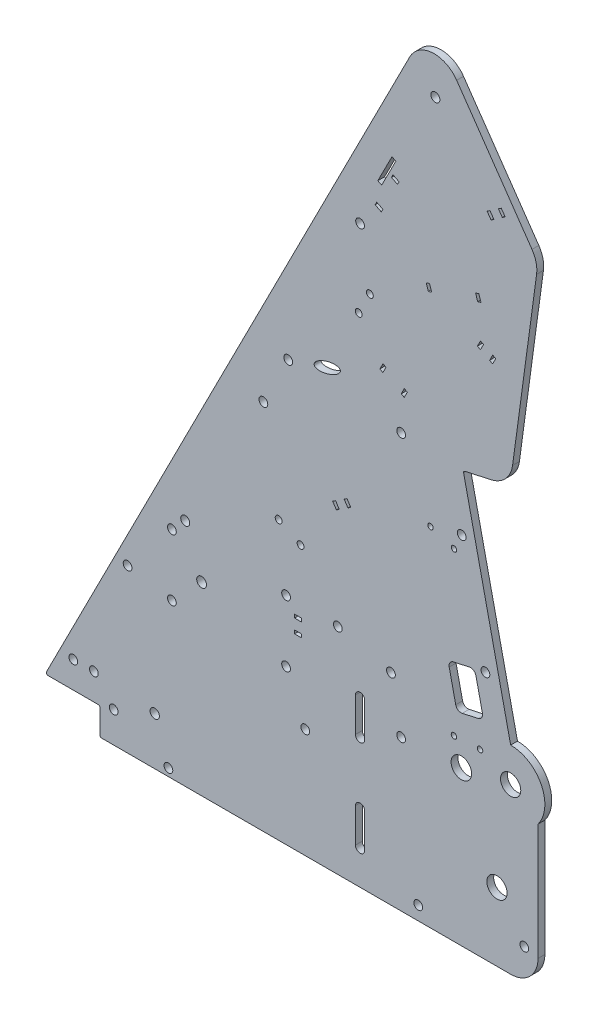
SolidWorks part; units mm, degrees
other "Markup1"
sketch "Sketch5"
ref_plane "Front Plane" through (0, 0, 0) normal (0, 0, 1) x (1, 0, 0)
ref_plane "Top Plane" through (0, 0, 0) normal (0, 1, 0) x (1, 0, 0)
ref_plane "Right Plane" through (0, 0, 0) normal (1, 0, 0) x (0, 0, -1)
sketch "Sketch1" plane through (0, 0, 0) normal (0, 0, 1) x (1, 0, 0)
  line L1 (228.6, -12.7) -> (228.6, 53.975)
  line L2 (178.7547, 351.4131) -> (0, 0)
  line L3 (228.6, 279.4) -> (178.7547, 351.4131)
  line L5 (0, 0) -> (25.4, 0)
  line L6 (25.4, 0) -> (25.4, -12.7)
  line L7 (25.4, -12.7) -> (228.6, -12.7)
  line L9 (215.9, 79.375) -> (193.9097, 178.5667)
  line L10 (193.9097, 178.5667) -> (215.6079, 183.377)
  line L11 (215.6079, 183.377) -> (228.6, 279.4)
  arc A0 (228.6, 53.975) -> (215.9, 79.375) centre (215.9, 63.5) ccw
  dimension "D7" = 12.7
  dimension "D8" = 76.2
  dimension "D10" = 31.75
  dimension "D2" = 292.1
  dimension "D3" = 25.4
  dimension "D4" = 215.9
  dimension "D5" = 394.2644
  dimension "D6" = 203.2
  dimension "D9" = 63.039
  dimension "D11" = 101.6
  dimension "D12" = 12.5
  dimension "D13" = 22.225
extrude "Boss-Extrude1" add sketch "Sketch1" along normal blind 3.175
sketch "Sketch2" plane through (0, 0, 3.175) normal (0, 0, 1) x (1, 0, 0)
  line L0 (178.7547, 351.4131) -> (0, 0) construction
  line L1 (25.4, -12.7) -> (228.6, -12.7) construction
  line L2 (215.9, 79.375) -> (193.9097, 178.5667) construction
  line L3 (193.9097, 178.5667) -> (215.6079, 183.377) construction
  line L4 (215.9, 79.375) -> (193.9097, 178.5667) construction
  line L5 (64.9432, 94.0578) -> (72.5445, 73.1732) construction
  line L6 (64.9432, 94.0578) -> (103.3734, 94.0578) construction
  line L10 (228.6, -12.7) -> (228.6, 53.975) construction
  circle A0 centre (64.9432, 94.0578) radius 2.0955
  circle A1 centre (180.975, 322.1643) radius 2.0955
  circle A2 centre (72.5445, 73.1732) radius 2.286
  circle A3 centre (193.2078, 152.3944) radius 2.032
  circle A4 centre (215.9, 63.5) radius 4.699
  circle A7 centre (173.0375, -6.35) radius 2.032
  circle A8 centre (204.203, 102.7985) radius 2.032
  circle A26 centre (209.55, 19.05) radius 4.699
  arc A30 (228.6, 53.975) -> (215.9, 79.375) centre (215.9, 63.5) ccw construction
  circle A31 centre (165.1, 179.3875) radius 2.032
  circle A35 centre (111.724, 87.4607) radius 2.032
  circle A36 centre (111.724, 58.8857) radius 2.032
  circle A37 centre (58.765, 58.8857) radius 2.032
  circle A38 centre (58.765, 87.4607) radius 2.032
  circle A39 centre (111.724, 58.8857) radius 1.905 construction
  circle A42 centre (111.724, 87.4607) radius 1.905 construction
  circle A43 centre (58.765, 58.8857) radius 1.905 construction
  circle A44 centre (58.765, 87.4607) radius 1.905 construction
  dimension "D3" = 4.191
  dimension "D5" = 4.191
  dimension "D9" = 4.572
  dimension "D20" = 9.398
  dimension "D23" = 9.398
  dimension "D18" = 4.064
  dimension "D26" = 4.064
  dimension "D14" = 4.064
  dimension "D10" = 4.064
  dimension "D2" = 15.24
  dimension "D6" = 15.24
  dimension "D7" = 22.225
  dimension "D21" = 44.45
  dimension "D22" = 6.35
  dimension "D19" = 160.3375
  dimension "D24" = 44.45
  dimension "D25" = 6.35
  dimension "D27" = 25.4
  dimension "D28" = 50.8
  dimension "D29" = 6.35
  dimension "D17" = 6.35
  dimension "D33" = 55.5625
  dimension "D15" = 114.3
  dimension "D4" = 180.975
  dimension "D8" = 70
extrude "Cut-Extrude1" cut sketch "Sketch2" against normal through all
sketch "Sketch7" plane through (0, 0, 3.175) normal (0, 0, 1) x (1, 0, 0)
  line L0 (146.05, 3.175) -> (146.05, 19.05) construction
  line L1 (143.891, 3.175) -> (143.891, 19.05)
  line L2 (148.209, 3.175) -> (148.209, 19.05)
  line L3 (146.05, 47.625) -> (146.05, 63.5) construction
  line L4 (143.891, 47.625) -> (143.891, 63.5)
  line L5 (148.209, 47.625) -> (148.209, 63.5)
  line L6 (25.4, -12.7) -> (228.6, -12.7) construction
  line L12 (228.6, -12.7) -> (228.6, 53.975) construction
  line L13 (25.4, -12.7) -> (228.6, -12.7) construction
  arc A0 (143.891, 3.175) -> (148.209, 3.175) centre (146.05, 3.175) ccw
  arc A1 (148.209, 19.05) -> (143.891, 19.05) centre (146.05, 19.05) ccw
  arc A2 (143.891, 47.625) -> (148.209, 47.625) centre (146.05, 47.625) ccw
  arc A3 (148.209, 63.5) -> (143.891, 63.5) centre (146.05, 63.5) ccw
  circle A8 centre (50.8, 9.525) radius 2.159
  point P2 (146.05, 11.1125)
  point P9 (146.05, 55.5625)
  dimension "D1" = 4.318
  dimension "D5" = 4.318
  dimension "D2" = 15.875
  dimension "D3" = 15.875
  dimension "D4" = 44.45
  dimension "D6" = 95.25
  dimension "D7" = 82.55
  dimension "D8" = 15.875
  dimension "D9" = 22.225
extrude "Cut-Extrude2" cut sketch "Sketch7" against normal through all
sketch "Sketch10" plane through (0, 0, 3.175) normal (0, 0, 1) x (1, 0, 0)
  circle A0 centre (120.65, 38.1) radius 2.032
  circle A1 centre (165.1, 57.15) radius 2.032
  circle A2 centre (13.0465, 12.3347) radius 2.032
  circle A3 centre (22.5715, 12.3347) radius 2.032
  circle A4 centre (38.2114, 62.6398) radius 2.032
  circle A5 centre (13.0465, 12.3347) radius 2.032 construction
  circle A6 centre (22.5715, 12.3347) radius 2.032 construction
  dimension "D1" = 4.064
  dimension "D3" = 38.1
  dimension "D2" = 120.65
  dimension "D4" = 63.5
  dimension "D5" = 69.85
extrude "Cut-Extrude3" cut sketch "Sketch10" against normal up to next
fillet "Fillet1" radius 12.7 4 edges at (228.6, -12.7, 1.5875) (178.7547, 351.4131, 1.5875) (215.6079, 183.377, 1.5875) (228.6, 279.4, 1.5875)
fillet "Fillet2" radius 0.7937 4 edges at (25.4, -12.7, 1.5875) (25.4, 0, 1.5875) (193.9097, 178.5667, 1.5875) (0, 0, 1.5875)
sketch "Sketch12" plane through (0, 0, 3.175) normal (0, 0, 1) x (1, 0, 0)
  circle A0 centre (31.75, 1.5875) radius 2.032
  circle A1 centre (173.0375, -6.35) radius 2.032
  circle A2 centre (222.25, 1.5875) radius 2.032
  circle A3 centre (57.15, -9.2075) radius 2.032
  circle A4 centre (57.15, -9.2075) radius 2.286 construction
  dimension "D1" = 4.064
  dimension "D2" = 4.064
extrude "Cut-Extrude5" cut sketch "Sketch12" against normal through all
sketch "Sketch13" plane through (0, 0, 3.175) normal (0, 0, 1) x (1, 0, 0)
  line L1 (228.6, 0) -> (228.6, 53.975) construction
  line L2 (1.2943, 0) -> (24.6062, 0) construction
  line L3 (26.1937, -12.7) -> (215.9, -12.7) construction
  line L8 (178.2697, 245.9923) -> (176.7582, 245.5069)
  line L9 (179.2404, 242.9693) -> (178.2697, 245.9923)
  line L10 (177.7289, 242.4839) -> (179.2404, 242.9693)
  line L11 (176.7582, 245.5069) -> (177.7289, 242.4839)
  line L12 (178.2697, 245.9923) -> (176.7582, 245.5069)
  line L13 (179.2404, 242.9693) -> (178.2697, 245.9923)
  line L14 (177.7289, 242.4839) -> (179.2404, 242.9693)
  line L15 (176.7582, 245.5069) -> (177.7289, 242.4839)
  line L16 (160.8477, 288.1984) -> (154.2836, 275.294)
  line L17 (200.6096, 249.8308) -> (202.1211, 250.3161)
  line L18 (199.639, 252.8538) -> (200.6096, 249.8308)
  line L19 (201.1505, 253.3391) -> (199.639, 252.8538)
  line L20 (202.1211, 250.3161) -> (201.1505, 253.3391)
  line L21 (200.6096, 249.8308) -> (202.1211, 250.3161)
  line L22 (199.639, 252.8538) -> (200.6096, 249.8308)
  line L23 (201.1505, 253.3391) -> (199.639, 252.8538)
  line L24 (202.1211, 250.3161) -> (201.1505, 253.3391)
  line L25 (160.8477, 288.1984) -> (162.6303, 287.2917)
  line L26 (160.5905, 279.7801) -> (163.4204, 278.3406)
  line L27 (161.3102, 281.1951) -> (160.5905, 279.7801)
  line L28 (164.1402, 279.7556) -> (161.3102, 281.1951)
  line L29 (163.4204, 278.3406) -> (164.1402, 279.7556)
  line L30 (160.5905, 279.7801) -> (163.4204, 278.3406)
  line L31 (161.3102, 281.1951) -> (160.5905, 279.7801)
  line L32 (164.1402, 279.7556) -> (161.3102, 281.1951)
  line L33 (163.4204, 278.3406) -> (164.1402, 279.7556)
  line L34 (154.2836, 275.294) -> (156.0662, 274.3872)
  line L35 (162.6303, 287.2917) -> (156.0662, 274.3872)
  line L36 (153.7897, 266.4104) -> (153.0699, 264.9954)
  line L37 (156.6196, 264.9709) -> (153.7897, 266.4104)
  line L38 (155.8998, 263.5559) -> (156.6196, 264.9709)
  line L39 (153.0699, 264.9954) -> (155.8998, 263.5559)
  line L40 (153.7897, 266.4104) -> (153.0699, 264.9954)
  line L41 (156.6196, 264.9709) -> (153.7897, 266.4104)
  line L42 (155.8998, 263.5559) -> (156.6196, 264.9709)
  line L43 (153.0699, 264.9954) -> (155.8998, 263.5559)
  line L110 (153.9925, 274.7218) -> (157.3929, 281.4066) construction
  line L111 (155.7751, 273.815) -> (159.1755, 280.4999) construction
  line L122 (203.3303, 234.0299) -> (201.9154, 234.7497)
  line L123 (201.8908, 231.2) -> (203.3303, 234.0299)
  line L124 (200.4759, 231.9198) -> (201.8908, 231.2)
  line L125 (201.9154, 234.7497) -> (200.4759, 231.9198)
  line L126 (203.3303, 234.0299) -> (201.9154, 234.7497)
  line L127 (201.8908, 231.2) -> (203.3303, 234.0299)
  line L128 (200.4759, 231.9198) -> (201.8908, 231.2)
  line L129 (201.9154, 234.7497) -> (200.4759, 231.9198)
  line L130 (206.1357, 229.0407) -> (207.5507, 228.321)
  line L131 (207.5752, 231.8707) -> (206.1357, 229.0407)
  line L132 (208.9902, 231.1509) -> (207.5752, 231.8707)
  line L133 (207.5507, 228.321) -> (208.9902, 231.1509)
  line L134 (206.1357, 229.0407) -> (207.5507, 228.321)
  line L135 (207.5752, 231.8707) -> (206.1357, 229.0407)
  line L136 (208.9902, 231.1509) -> (207.5752, 231.8707)
  line L137 (207.5507, 228.321) -> (208.9902, 231.1509)
  line L138 (211.5405, 292.889) -> (210.2352, 291.9855)
  line L139 (213.3475, 290.2784) -> (211.5405, 292.889)
  line L140 (212.0422, 289.3749) -> (213.3475, 290.2784)
  line L141 (210.2352, 291.9855) -> (212.0422, 289.3749)
  line L142 (211.5405, 292.889) -> (210.2352, 291.9855)
  line L143 (213.3475, 290.2784) -> (211.5405, 292.889)
  line L144 (212.0422, 289.3749) -> (213.3475, 290.2784)
  line L145 (210.2352, 291.9855) -> (212.0422, 289.3749)
  line L146 (206.3193, 289.275) -> (205.014, 288.3715)
  line L147 (208.1263, 286.6644) -> (206.3193, 289.275)
  line L148 (206.821, 285.7609) -> (208.1263, 286.6644)
  line L149 (205.014, 288.3715) -> (206.821, 285.7609)
  line L150 (206.3193, 289.275) -> (205.014, 288.3715)
  line L151 (208.1263, 286.6644) -> (206.3193, 289.275)
  line L152 (206.821, 285.7609) -> (208.1263, 286.6644)
  line L153 (205.014, 288.3715) -> (206.821, 285.7609)
  line L184 (133.3504, 136.102) -> (135.0815, 133.4404)
  line L185 (133.3504, 136.102) -> (134.6812, 136.9675)
  line L186 (135.0815, 133.4404) -> (136.4123, 134.3059)
  line L187 (155.2281, 200.1197) -> (156.643, 199.3999)
  line L188 (156.6676, 202.9496) -> (155.2281, 200.1197)
  line L189 (158.0826, 202.2298) -> (156.6676, 202.9496)
  line L190 (156.643, 199.3999) -> (158.0826, 202.2298)
  line L191 (155.2281, 200.1197) -> (156.643, 199.3999)
  line L192 (156.6676, 202.9496) -> (155.2281, 200.1197)
  line L193 (158.0826, 202.2298) -> (156.6676, 202.9496)
  line L194 (156.643, 199.3999) -> (158.0826, 202.2298)
  line L195 (134.6812, 136.9675) -> (136.4123, 134.3059)
  line L196 (165.1328, 195.0814) -> (166.5478, 194.3617)
  line L197 (166.5723, 197.9113) -> (165.1328, 195.0814)
  line L198 (167.9873, 197.1916) -> (166.5723, 197.9113)
  line L199 (166.5478, 194.3617) -> (167.9873, 197.1916)
  line L200 (165.1328, 195.0814) -> (166.5478, 194.3617)
  line L201 (166.5723, 197.9113) -> (165.1328, 195.0814)
  line L202 (167.9873, 197.1916) -> (166.5723, 197.9113)
  line L203 (166.5478, 194.3617) -> (167.9873, 197.1916)
  line L204 (140.4047, 136.9025) -> (138.6737, 139.5641)
  line L205 (140.4047, 136.9025) -> (141.7355, 137.768)
  line L206 (138.6737, 139.5641) -> (140.0045, 140.4296)
  line L207 (141.7355, 137.768) -> (140.0045, 140.4296)
  line L209 (169.1053, 332.4434) -> (0.5868, 1.1536) construction
  line L210 (88.0466, 102.1523) -> (85.2167, 103.5918) construction
  line L288 (115.661, 81.8727) -> (118.836, 81.8727)
  line L289 (115.661, 81.8727) -> (115.661, 80.2852)
  line L290 (118.836, 81.8727) -> (118.836, 80.2852)
  line L291 (115.661, 80.2852) -> (118.836, 80.2852)
  line L292 (115.661, 75.5227) -> (118.836, 75.5227)
  line L293 (115.661, 75.5227) -> (115.661, 73.9352)
  line L294 (118.836, 75.5227) -> (118.836, 73.9352)
  line L295 (115.661, 73.9352) -> (118.836, 73.9352)
  line L297 (115.661, 86.2542) -> (115.661, 60.0922) construction
  line L298 (59.9715, 91.3977) -> (110.5175, 91.3977) construction
  circle A0 centre (112.7125, 182.5625) radius 2.032
  circle A1 centre (146.05, 254) radius 2.032
  circle A2 centre (101.1964, 159.9231) radius 2.032 construction
  circle A3 centre (101.1964, 159.9231) radius 2.032
  circle A4 centre (145.4254, 217.7376) radius 1.6 construction
  circle A5 centre (150.594, 227.8985) radius 1.6 construction
  circle A7 centre (145.4254, 217.7376) radius 1.6
  circle A8 centre (150.594, 227.8985) radius 1.6
  circle A9 centre (108.294, 116.1502) radius 1.6 construction
  circle A10 centre (118.455, 110.9816) radius 1.6 construction
  circle A11 centre (108.294, 116.1502) radius 1.6
  circle A12 centre (118.455, 110.9816) radius 1.6
  ellipse E0 centre (130.8261, 188.4615) end of major axis (136.864, 190.4279) minor radius 2.3812 construction
  ellipse E1 centre (130.8261, 188.4615) end of major axis (136.864, 190.4279) minor radius 2.3812
  dimension "D2" = 4.064
  dimension "D5" = 4.064
  dimension "D1" = 195.2625
  dimension "D3" = 82.55
  dimension "D4" = 254
  dimension "D6" = 115.8875
  dimension "D11" = 7.62
  dimension "D12" = 6.858
  dimension "D13" = 1.5875
  dimension "D14" = 3.175
  dimension "D15" = 4.7625
  dimension "D16" = 60
  dimension "D17" = 57.15
  dimension "D24" = 50.8
  dimension "D29" = 3.175
  dimension "D30" = 1.5875
  dimension "D31" = 4.7625
  dimension "D32" = 0
  dimension "D33" = 9.525
  dimension "D7" = 0
  dimension "D8" = 0
  dimension "D9" = 0
  dimension "D10" = 0
  dimension "D18" = 0
  dimension "D19" = 0
  dimension "D20" = 0
  dimension "D21" = 0
  dimension "D22" = 0
  dimension "D23" = 0
extrude "Cut-Extrude6" cut sketch "Sketch13" against normal through all
sketch "Sketch14" plane through (0, 0, 3.175) normal (0, 0, 1) x (1, 0, 0)
  line L5 (186.8444, 98.9502) -> (199.2434, 101.699)
  line L6 (186.8444, 98.9502) -> (190.9676, 80.3518)
  line L7 (190.9676, 80.3518) -> (203.3665, 83.1006)
  line L8 (199.2434, 101.699) -> (203.3665, 83.1006)
  line L14 (202.8168, 85.5804) -> (199.7931, 99.2192) construction
  line L15 (193.4474, 80.9015) -> (200.8868, 82.5508) construction
  line L16 (187.3942, 96.4704) -> (190.4178, 82.8316) construction
  line L17 (196.7636, 101.1493) -> (189.3242, 99.5) construction
  circle A0 centre (189.6022, 69.9806) radius 1.27
  circle A1 centre (201.7089, 70.5092) radius 1.27
  circle A2 centre (189.6022, 69.9806) radius 1.27 construction
  circle A3 centre (201.7089, 70.5092) radius 1.27 construction
  circle A4 centre (160.3714, 80.7296) radius 2.032
  circle A5 centre (135.7298, 86.89) radius 2.032
  circle A6 centre (178.7216, 148.5324) radius 1.27
  circle A8 centre (178.7216, 148.5324) radius 1.27 construction
  circle A9 centre (189.6226, 145.0954) radius 1.27
  circle A10 centre (189.6226, 145.0954) radius 1.27 construction
  point P8 (152.4, 88.9)
  dimension "D1" = 4.064
extrude "Cut-Extrude7" cut sketch "Sketch14" against normal through all both and the other way through all
fillet "Fillet3" radius 2.54 4 edges at (199.2434, 101.699, 1.5875) (186.8444, 98.9502, 1.5875) (190.9676, 80.3518, 1.5875) (203.3665, 83.1006, 1.5875)
sketch "Sketch15" plane through (0, 0, 3.175) normal (0, 0, 1) x (1, 0, 0)
  circle A0 centre (193.04, 58.801) radius 4.7625 construction
  circle A1 centre (193.04, 58.801) radius 4.7625
extrude "Cut-Extrude8" cut sketch "Sketch15" against normal through all
equation "\"D6@Sketch2\"=\"D2@Sketch2\""
